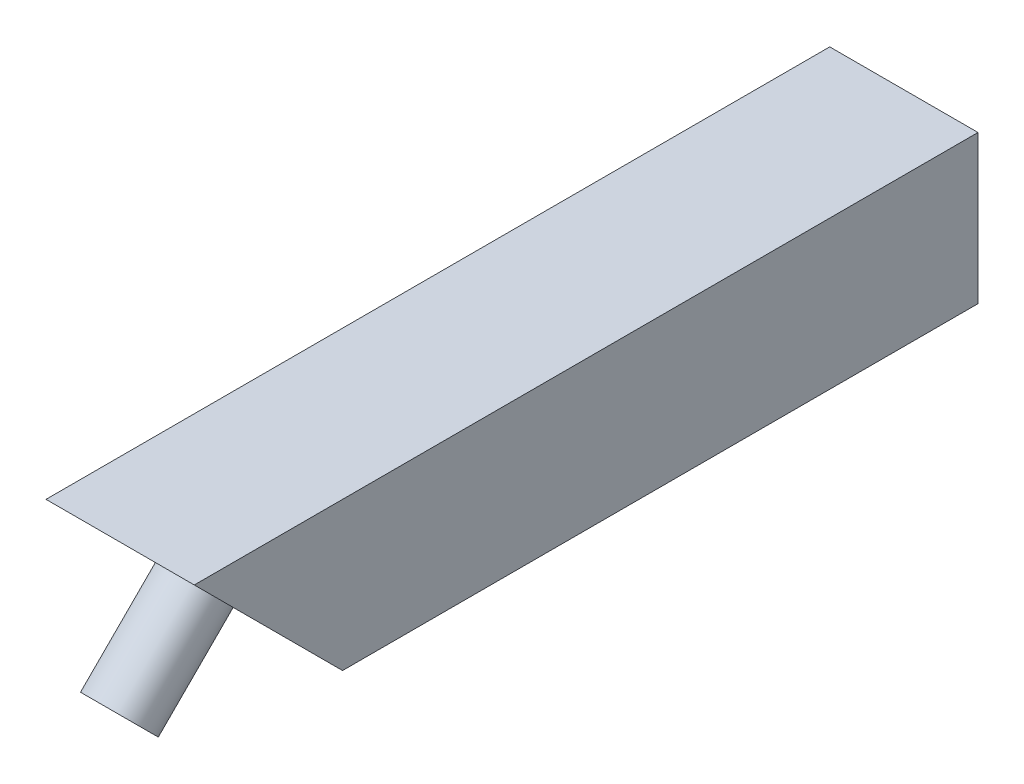
SolidWorks part; units mm, degrees
ref_plane "Front Plane" through (0, 0, 0) normal (0, 0, 1) x (1, 0, 0)
ref_plane "Top Plane" through (0, 0, 0) normal (0, 1, 0) x (1, 0, 0)
ref_plane "Right Plane" through (0, 0, 0) normal (1, 0, 0) x (0, 0, -1)
sketch "Sketch1" plane through (0, 0, 0) normal (0, 0, 1) x (1, 0, 0)
  line L1 (0, 0) -> (7, 0)
  line L2 (0, 0) -> (0, 7)
  line L3 (0, 7) -> (7, 7)
  line L4 (7, 0) -> (7, 7)
  dimension "D1" = 7
  dimension "D2" = 7
extrude "Boss-Extrude1" add sketch "Sketch1" along normal blind 20
sketch "Sketch3" plane through (7, 0, 0) normal (1, 0, 0) x (0, 0, -1)
  line L0 (-20, 7) -> (-27, 7)
  line L1 (-27, 7) -> (-20, 0)
  line L2 (-20, 0) -> (-20, 7)
extrude "Boss-Extrude2" add sketch "Sketch3" against normal blind 7
sketch "Sketch4" plane through (0, -10, 10) normal (0, -0.7071, 0.7071) x (1, 0, 0)
  circle A0 centre (3.5, 19.0919) radius 1.5
  dimension "D1" = 3
extrude "Boss-Extrude3" add sketch "Sketch4" along normal blind 5
sketch "Sketch5" plane through (0, 0, 0) normal (0, 0, -1) x (-1, 0, 0)
  line L1 (-7, 0) -> (0, 0)
  line L2 (-7, 0) -> (-7, 7)
  line L3 (-7, 7) -> (0, 7)
  line L4 (0, 0) -> (0, 7)
extrude "Boss-Extrude4" add sketch "Sketch5" along normal blind 10
